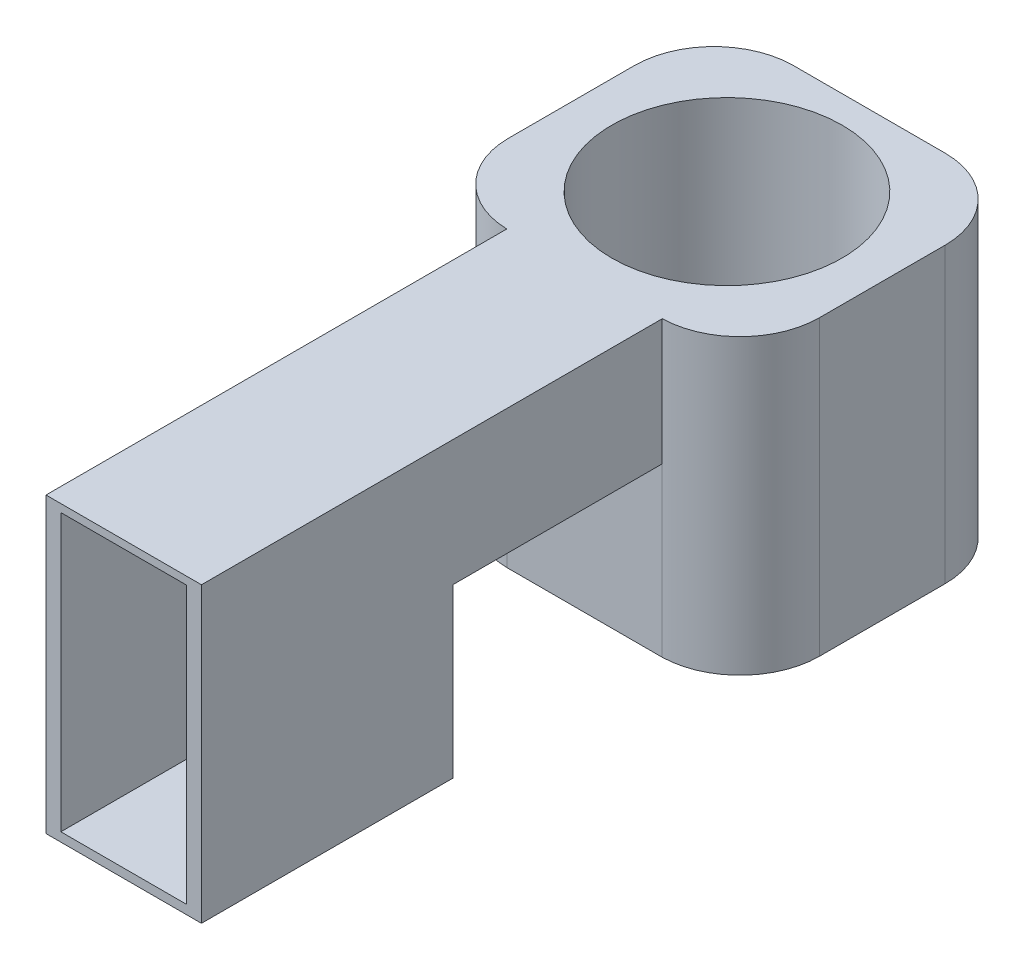
SolidWorks part; units mm, degrees
ref_plane "Front Plane" through (0, 0, 0) normal (0, 0, 1) x (1, 0, 0)
ref_plane "Top Plane" through (0, 0, 0) normal (0, 1, 0) x (1, 0, 0)
ref_plane "Right Plane" through (0, 0, 0) normal (1, 0, 0) x (0, 0, -1)
sketch "Sketch1" plane through (0, 0, 0) normal (0, 1, 0) x (1, 0, 0)
  line L0 (-74.2237, 0) -> (-37.1118, -68) construction
  line L1 (0, 0) -> (-74.2237, 0)
  line L2 (0, 0) -> (0, -68)
  line L3 (0, -68) -> (-74.2237, -68)
  line L4 (-74.2237, 0) -> (-74.2237, -68)
  line L5 (-37.1118, -68) -> (0, 0) construction
  line L6 (-55.6678, -34) -> (-55.6678, -68) construction
  line L7 (-18.5559, -34) -> (-18.5559, -68) construction
  line L8 (-55.6678, -68) -> (-55.6678, -120)
  line L9 (-55.6678, -120) -> (-18.5559, -120)
  line L10 (-18.5559, -120) -> (-18.5559, -68)
  line L12 (-18.5559, -120) -> (-55.6678, -120)
  line L13 (-18.5559, -120) -> (-18.5559, -178)
  line L14 (-18.5559, -178) -> (-55.6678, -178)
  line L15 (-55.6678, -120) -> (-55.6678, -178)
  dimension "D1" = 120
  dimension "D2" = 68
  dimension "D3" = 58
  dimension "D4" = 18.5559
extrude "Boss-Extrude1" add sketch "Sketch1" against normal blind 70 contours L1 L4 L3 L2 | L9 L10 L3 L8 | L9 L15 L14 L13 region at (-37.1118, 0, 34) region at (-37.1118, 0, 94) region at (-37.1118, 0, 149)
sketch "Sketch2" plane through (0, 0, 0) normal (0, 1, 0) x (1, 0, 0)
  line L0 (-55.6678, -68) -> (-18.5559, -68) construction
  line L1 (-37.1118, -68) -> (-37.1118, 0) construction
  line L2 (0, 0) -> (-74.2237, 0) construction
  circle A0 centre (-37.1118, -34) radius 27.5
  dimension "D1" = 55
extrude "Cut-Extrude1" cut sketch "Sketch2" against normal blind 70
fillet "Fillet1" radius 19 4 edges at (0, -35, 68) (0, -35, 0) (-74.2237, -35, 68) (-74.2237, -35, 0)
sketch "Sketch3" plane through (0, 0, 178) normal (0, 0, 1) x (1, 0, 0)
  line L0 (-18.5559, 0) -> (-55.6678, 0) construction
  line L1 (-20.5559, -3.7111) -> (-53.6678, -3.7111)
  line L2 (-20.5559, -3.7111) -> (-20.5559, -68)
  line L3 (-20.5559, -68) -> (-53.6678, -68)
  line L4 (-53.6678, -3.7111) -> (-53.6678, -68)
  line L5 (-18.5559, -70) -> (-55.6678, -70) construction
  line L6 (-55.6678, -70) -> (-55.6678, 0) construction
  line L7 (-18.5559, -70) -> (-18.5559, 0) construction
  dimension "D1" = 3.7111
  dimension "D2" = 2
  dimension "D3" = 2
  dimension "D4" = 2
extrude "Cut-Extrude2" cut sketch "Sketch3" against normal blind 58
sketch "Sketch5" plane through (-55.6678, 0, 0) normal (-1, 0, 0) x (0, 0, 1)
  line L0 (68, 0) -> (178, 0) construction
  line L1 (68, -70) -> (118, -70)
  line L2 (68, -70) -> (68, -30)
  line L3 (68, -30) -> (118, -30)
  line L4 (118, -70) -> (118, -30)
  line L5 (120, -3.7111) -> (120, -68) construction
  dimension "D1" = 30
  dimension "D2" = 2
extrude "Cut-Extrude3" cut sketch "Sketch5" against normal blind 58
sketch "Sketch7" plane through (0, 0, 118) normal (0, 0, -1) x (-1, 0, 0)
  line L0 (18.5559, -70) -> (55.6678, -70) construction
  line L1 (22.5559, -41.3697) -> (52.0723, -41.3697)
  line L2 (22.5559, -41.3697) -> (22.5559, -60)
  line L3 (22.5559, -60) -> (52.0723, -60)
  line L4 (52.0723, -41.3697) -> (52.0723, -60)
  line L5 (55.6678, -70) -> (55.6678, -30) construction
  line L6 (20.5559, -68) -> (20.5559, -3.7111) construction
  dimension "D1" = 10
  dimension "D2" = 3.5955
  dimension "D3" = 2
extrude "Cut-Extrude5" cut sketch "Sketch7" against normal blind 58
sketch "Sketch8" plane through (0, 0, 178) normal (0, 0, 1) x (1, 0, 0)
  line L1 (-53.6678, -3.7111) -> (-20.5559, -3.7111)
  line L2 (-53.6678, -3.7111) -> (-53.6678, -1.7111)
  line L3 (-53.6678, -1.7111) -> (-20.5559, -1.7111)
  line L4 (-20.5559, -3.7111) -> (-20.5559, -1.7111)
  dimension "D1" = 2
extrude "Cut-Extrude6" cut sketch "Sketch8" against normal blind 58
sketch "Sketch9" plane through (0, 0, 178) normal (0, 0, 1) x (1, 0, 0)
  line L0 (-20.5559, -1.7111) -> (-53.6678, -1.7111) construction
  line L1 (-53.6678, -68) -> (-52.1178, -68)
  line L2 (-53.6678, -68) -> (-53.6678, -1.7111)
  line L3 (-53.6678, -1.7111) -> (-52.1178, -1.7111)
  line L4 (-52.1178, -68) -> (-52.1178, -1.7111)
  line L6 (-20.5559, -68) -> (-22.1059, -68)
  line L7 (-20.5559, -68) -> (-20.5559, -1.7111)
  line L8 (-20.5559, -1.7111) -> (-22.1059, -1.7111)
  line L9 (-22.1059, -68) -> (-22.1059, -1.7111)
  dimension "D1" = 1.55
  dimension "D2" = 1.55
extrude "Boss-Extrude2" add sketch "Sketch9" against normal blind 58
sketch "Sketch10" plane through (0, 0, 178) normal (0, 0, 1) x (1, 0, 0)
  line L0 (-22.1059, -1.7111) -> (-22.1059, -68) construction
  line L1 (-52.1178, -68) -> (-22.1059, -68)
  line L2 (-52.1178, -68) -> (-52.1178, -67.855)
  line L3 (-52.1178, -67.855) -> (-22.1059, -67.855)
  line L4 (-22.1059, -68) -> (-22.1059, -67.855)
  line L6 (-52.1178, -1.7111) -> (-22.1059, -1.7111)
  line L7 (-52.1178, -1.7111) -> (-52.1178, -1.8561)
  line L8 (-52.1178, -1.8561) -> (-22.1059, -1.8561)
  line L9 (-22.1059, -1.7111) -> (-22.1059, -1.8561)
  dimension "D1" = 0.145
  dimension "D2" = 0.145
extrude "Boss-Extrude3" add sketch "Sketch10" against normal blind 58
